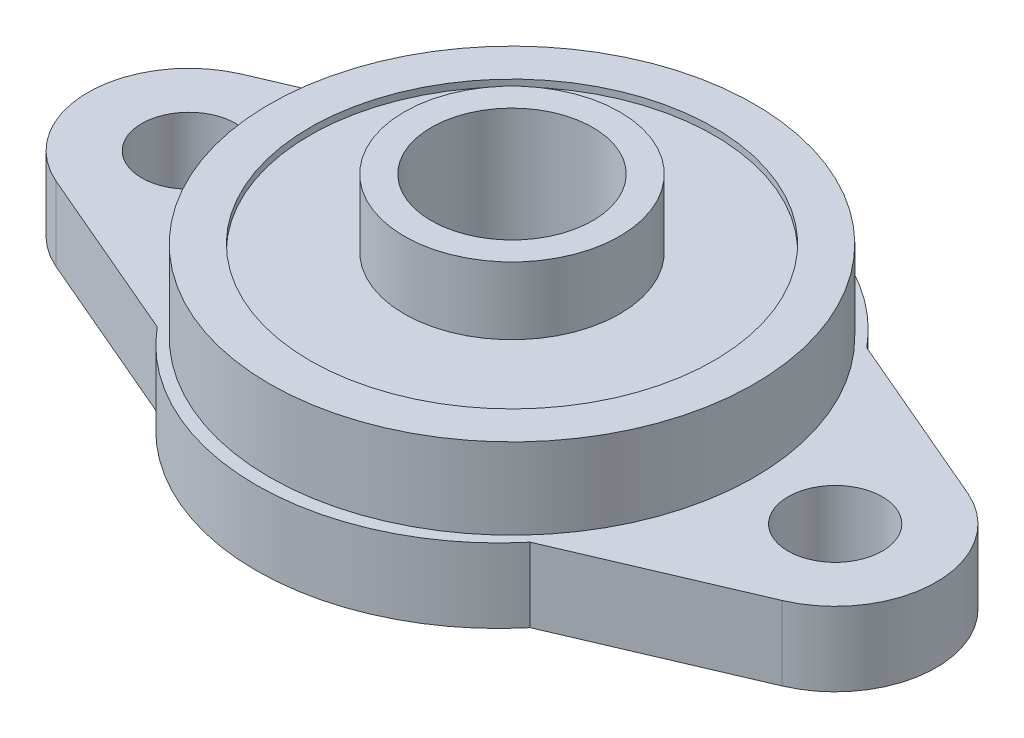
SolidWorks part; units mm, degrees
material "Zinc AC41A Alloy, As Cast"
ref_plane "Front Plane" through (0, 0, 0) normal (0, 0, 1) x (1, 0, 0)
ref_plane "Top Plane" through (0, 0, 0) normal (0, 1, 0) x (1, 0, 0)
ref_plane "Right Plane" through (0, 0, 0) normal (1, 0, 0) x (0, 0, -1)
sketch "Sketch1" plane through (0, 0, 0) normal (0, 1, 0) x (1, 0, 0)
  line L0 (-26.9496, 6.8957) -> (-13.8474, 12.5)
  line L1 (-26.9496, -6.8957) -> (-13.8474, -12.5)
  line L2 (0, 19) -> (0, -19) construction
  line L3 (26.9496, -6.8957) -> (13.8474, -12.5)
  line L4 (26.9496, 6.8957) -> (13.8474, 12.5)
  line L5 (-31.5, 0) -> (31.5, 0) construction
  circle A0 centre (0, 0) radius 6
  circle A1 centre (-24, 0) radius 3.5
  arc A3 (-26.9496, 6.8957) -> (-26.9496, -6.8957) centre (-24, 0) ccw
  arc A4 (-13.8474, 12.5) -> (13.8474, 12.5) centre (0, 1) cw
  arc A5 (-13.8474, -12.5) -> (13.8474, -12.5) centre (0, -1) ccw
  arc A6 (26.9496, 6.8957) -> (26.9496, -6.8957) centre (24, 0) cw
  circle A7 centre (24, 0) radius 3.5
  circle A8 centre (0, 0) radius 8
  circle A9 centre (0, 0) radius 15
  circle A10 centre (0, 0) radius 18
  point P21 (0, 0)
  point P23 (0, -19)
  point P24 (0, 19)
  dimension "D1" = 12
  dimension "D3" = 48
  dimension "D5" = 7
  dimension "D6" = 16
  dimension "D7" = 30
  dimension "D8" = 36
  dimension "D9" = 18
  dimension "D2" = 63
  dimension "D4" = 38
  dimension "D10" = 25
extrude "Boss-Extrude1" add sketch "Sketch1" against normal blind 5.5 contours A6 L4 A4 L0 A3 L1 A5 L3 A10 A1 A7 | A10 A9 | A9 A8 | A8 A0 region at (-20.1091, 0, -9.0214) region at (-7.7737, 0, 0) region at (-14.5757, 0, 0) region at (-17.4909, 0, 0)
extrude "Boss-Extrude2" add sketch "Sketch1<3>" along normal blind 6 contours A10 A9 region at (-17.4909, 0, 0)
sketch "Sketch1<3>" plane through (0, 0, 0) normal (0, 1, 0) x (1, 0, 0) same geometry as "Sketch1"
extrude "Boss-Extrude3" add sketch "Sketch1<4>" along normal blind 5.5 contours A9 A8 region at (-14.5757, 0, 0)
sketch "Sketch1<4>" plane through (0, 0, 0) normal (0, 1, 0) x (1, 0, 0) same geometry as "Sketch1"
extrude "Boss-Extrude4" add sketch "Sketch1<5>" along normal blind 10.5 contours A8 A0 region at (-7.7737, 0, 0)
sketch "Sketch1<5>" plane through (0, 0, 0) normal (0, 1, 0) x (1, 0, 0) same geometry as "Sketch1"
sketch "Sketch2" plane through (0, -5.5, 0) normal (0, -1, 0) x (1, 0, 0)
  circle A0 centre (0, 0) radius 8
  circle A1 centre (0, 0) radius 15
  circle A2 centre (0, 0) radius 15 construction
  circle A3 centre (0, 0) radius 8 construction
extrude "Cut-Extrude1" cut sketch "Sketch2" against normal blind 0.5
